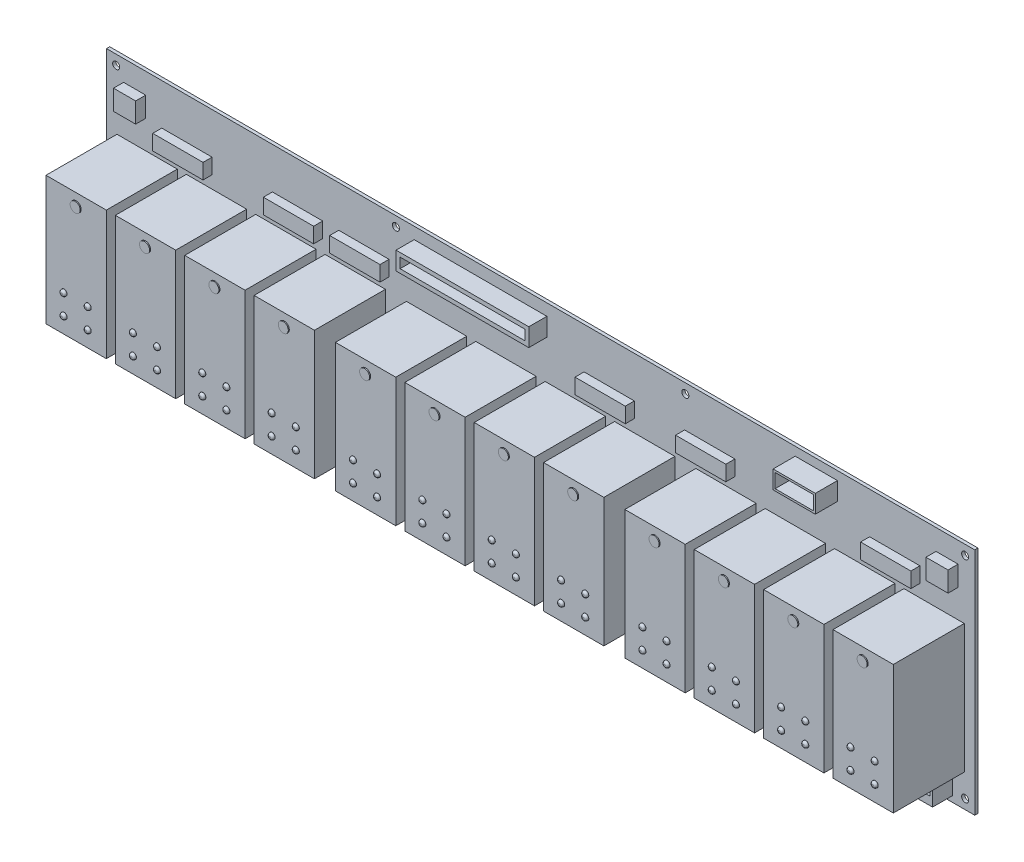
SolidWorks part; units mm, degrees
ref_plane "Front Plane" through (0, 0, 0) normal (0, 0, 1) x (1, 0, 0)
ref_plane "Top Plane" through (0, 0, 0) normal (0, 1, 0) x (1, 0, 0)
ref_plane "Right Plane" through (0, 0, 0) normal (1, 0, 0) x (0, 0, -1)
sketch "Sketch1" plane through (0, 0, 0) normal (0, 0, 1) x (1, 0, 0)
  line L1 (0, 0) -> (431.8, 0)
  line L2 (0, 0) -> (0, 114.3)
  line L3 (0, 114.3) -> (431.8, 114.3)
  line L4 (431.8, 0) -> (431.8, 114.3)
extrude "PCB" add sketch "Sketch1" along normal blind 1.6
ref_plane "Plane_z1_6" through (0, 0, 1.6) normal (0, 0, 1) x (1, 0, 0)
sketch "Sketch2" plane through (0, 0, 1.6) normal (0, 0, 1) x (1, 0, 0)
  line L1 (27.5, 86.2) -> (52.5, 86.2)
  line L2 (27.5, 86.2) -> (27.5, 93.8)
  line L3 (27.5, 93.8) -> (52.5, 93.8)
  line L4 (52.5, 86.2) -> (52.5, 93.8)
  line L6 (82.5, 86.2) -> (107.5, 86.2)
  line L7 (82.5, 86.2) -> (82.5, 93.8)
  line L8 (82.5, 93.8) -> (107.5, 93.8)
  line L9 (107.5, 86.2) -> (107.5, 93.8)
  line L11 (115.5, 86.2) -> (140.5, 86.2)
  line L12 (115.5, 86.2) -> (115.5, 93.8)
  line L13 (115.5, 93.8) -> (140.5, 93.8)
  line L14 (140.5, 86.2) -> (140.5, 93.8)
  line L16 (237.5, 86.2) -> (262.5, 86.2)
  line L17 (237.5, 86.2) -> (237.5, 93.8)
  line L18 (237.5, 93.8) -> (262.5, 93.8)
  line L19 (262.5, 86.2) -> (262.5, 93.8)
  line L21 (287.5, 86.2) -> (312.5, 86.2)
  line L22 (287.5, 86.2) -> (287.5, 93.8)
  line L23 (287.5, 93.8) -> (312.5, 93.8)
  line L24 (312.5, 86.2) -> (312.5, 93.8)
  line L26 (379.5, 86.2) -> (404.5, 86.2)
  line L27 (379.5, 86.2) -> (379.5, 93.8)
  line L28 (379.5, 93.8) -> (404.5, 93.8)
  line L29 (404.5, 86.2) -> (404.5, 93.8)
extrude "Body00" add sketch "Sketch2" along normal blind 4.5
sketch "Sketch3" plane through (0, 0, 1.6) normal (0, 0, 1) x (1, 0, 0)
  line L1 (8.5, 94) -> (19.5, 94)
  line L2 (8.5, 94) -> (8.5, 104)
  line L3 (8.5, 104) -> (19.5, 104)
  line L4 (19.5, 94) -> (19.5, 104)
  line L6 (412.5, 94) -> (423.5, 94)
  line L7 (412.5, 94) -> (412.5, 104)
  line L8 (412.5, 104) -> (423.5, 104)
  line L9 (423.5, 94) -> (423.5, 104)
extrude "Body01" add sketch "Sketch3" along normal blind 5
sketch "Sketch4" plane through (0, 0, 1.6) normal (0, 0, 1) x (1, 0, 0)
  line L1 (153, 99.5) -> (219, 99.5)
  line L2 (153, 99.5) -> (153, 108.5)
  line L3 (153, 108.5) -> (219, 108.5)
  line L4 (219, 99.5) -> (219, 108.5)
extrude "Body02" add sketch "Sketch4" along normal blind 9
sketch "Sketch5" plane through (0, 0, 1.6) normal (0, 0, 1) x (1, 0, 0)
  line L1 (11.007, 3) -> (132.927, 3)
  line L2 (11.007, 3) -> (11.007, 12)
  line L3 (11.007, 12) -> (132.927, 12)
  line L4 (132.927, 3) -> (132.927, 12)
  line L6 (154.94, 3) -> (276.86, 3)
  line L7 (154.94, 3) -> (154.94, 12)
  line L8 (154.94, 12) -> (276.86, 12)
  line L9 (276.86, 3) -> (276.86, 12)
  line L11 (298.873, 3) -> (420.793, 3)
  line L12 (298.873, 3) -> (298.873, 12)
  line L13 (298.873, 12) -> (420.793, 12)
  line L14 (420.793, 3) -> (420.793, 12)
extrude "Body03" add sketch "Sketch5" along normal blind 10
sketch "Sketch6" plane through (0, 0, 1.6) normal (0, 0, 1) x (1, 0, 0)
  line L1 (342.5, 101) -> (363.5, 101)
  line L2 (342.5, 101) -> (342.5, 110)
  line L3 (342.5, 110) -> (363.5, 110)
  line L4 (363.5, 101) -> (363.5, 110)
extrude "Body04" add sketch "Sketch6" along normal blind 11
sketch "Sketch7" plane through (0, 0, 1.6) normal (0, 0, 1) x (1, 0, 0)
  line L1 (5.217, 16) -> (35.217, 16)
  line L2 (5.217, 16) -> (5.217, 80)
  line L3 (5.217, 80) -> (35.217, 80)
  line L4 (35.217, 16) -> (35.217, 80)
  line L6 (39.717, 16) -> (69.717, 16)
  line L7 (39.717, 16) -> (39.717, 80)
  line L8 (39.717, 80) -> (69.717, 80)
  line L9 (69.717, 16) -> (69.717, 80)
  line L11 (74.217, 16) -> (104.217, 16)
  line L12 (74.217, 16) -> (74.217, 80)
  line L13 (74.217, 80) -> (104.217, 80)
  line L14 (104.217, 16) -> (104.217, 80)
  line L16 (108.717, 16) -> (138.717, 16)
  line L17 (108.717, 16) -> (108.717, 80)
  line L18 (108.717, 80) -> (138.717, 80)
  line L19 (138.717, 16) -> (138.717, 80)
  line L21 (149.15, 16) -> (179.15, 16)
  line L22 (149.15, 16) -> (149.15, 80)
  line L23 (149.15, 80) -> (179.15, 80)
  line L24 (179.15, 16) -> (179.15, 80)
  line L26 (183.65, 16) -> (213.65, 16)
  line L27 (183.65, 16) -> (183.65, 80)
  line L28 (183.65, 80) -> (213.65, 80)
  line L29 (213.65, 16) -> (213.65, 80)
  line L31 (218.15, 16) -> (248.15, 16)
  line L32 (218.15, 16) -> (218.15, 80)
  line L33 (218.15, 80) -> (248.15, 80)
  line L34 (248.15, 16) -> (248.15, 80)
  line L36 (252.65, 16) -> (282.65, 16)
  line L37 (252.65, 16) -> (252.65, 80)
  line L38 (252.65, 80) -> (282.65, 80)
  line L39 (282.65, 16) -> (282.65, 80)
  line L41 (293.083, 16) -> (323.083, 16)
  line L42 (293.083, 16) -> (293.083, 80)
  line L43 (293.083, 80) -> (323.083, 80)
  line L44 (323.083, 16) -> (323.083, 80)
  line L46 (327.583, 16) -> (357.583, 16)
  line L47 (327.583, 16) -> (327.583, 80)
  line L48 (327.583, 80) -> (357.583, 80)
  line L49 (357.583, 16) -> (357.583, 80)
  line L51 (362.083, 16) -> (392.083, 16)
  line L52 (362.083, 16) -> (362.083, 80)
  line L53 (362.083, 80) -> (392.083, 80)
  line L54 (392.083, 16) -> (392.083, 80)
  line L56 (396.583, 16) -> (426.583, 16)
  line L57 (396.583, 16) -> (396.583, 80)
  line L58 (396.583, 80) -> (426.583, 80)
  line L59 (426.583, 16) -> (426.583, 80)
extrude "Body05" add sketch "Sketch7" along normal blind 35.3
ref_plane "Plane_z36_9" through (0, 0, 36.9) normal (0, 0, 1) x (1, 0, 0)
sketch "Sketch8" plane through (0, 0, 36.9) normal (0, 0, 1) x (1, 0, 0)
  circle A0 centre (20.217, 74) radius 2.5
  circle A1 centre (54.717, 74) radius 2.5
  circle A2 centre (89.217, 74) radius 2.5
  circle A3 centre (123.717, 74) radius 2.5
  circle A4 centre (164.15, 74) radius 2.5
  circle A5 centre (198.65, 74) radius 2.5
  circle A6 centre (233.15, 74) radius 2.5
  circle A7 centre (267.65, 74) radius 2.5
  circle A8 centre (308.083, 74) radius 2.5
  circle A9 centre (342.583, 74) radius 2.5
  circle A10 centre (377.083, 74) radius 2.5
  circle A11 centre (411.583, 74) radius 2.5
extrude "Body06" add sketch "Sketch8" along normal blind 0.5
sketch "Sketch9" plane through (0, 0, 36.9) normal (0, 0, 1) x (1, 0, 0)
  circle A0 centre (14.217, 24) radius 1.5
  circle A1 centre (14.217, 34) radius 1.5
  circle A2 centre (26.217, 24) radius 1.5
  circle A3 centre (26.217, 34) radius 1.5
  circle A4 centre (48.717, 24) radius 1.5
  circle A5 centre (48.717, 34) radius 1.5
  circle A6 centre (60.717, 24) radius 1.5
  circle A7 centre (60.717, 34) radius 1.5
  circle A8 centre (83.217, 24) radius 1.5
  circle A9 centre (83.217, 34) radius 1.5
  circle A10 centre (95.217, 24) radius 1.5
  circle A11 centre (95.217, 34) radius 1.5
  circle A12 centre (117.717, 24) radius 1.5
  circle A13 centre (117.717, 34) radius 1.5
  circle A14 centre (129.717, 24) radius 1.5
  circle A15 centre (129.717, 34) radius 1.5
  circle A16 centre (158.15, 24) radius 1.5
  circle A17 centre (158.15, 34) radius 1.5
  circle A18 centre (170.15, 24) radius 1.5
  circle A19 centre (170.15, 34) radius 1.5
  circle A20 centre (192.65, 24) radius 1.5
  circle A21 centre (192.65, 34) radius 1.5
  circle A22 centre (204.65, 24) radius 1.5
  circle A23 centre (204.65, 34) radius 1.5
  circle A24 centre (227.15, 24) radius 1.5
  circle A25 centre (227.15, 34) radius 1.5
  circle A26 centre (239.15, 24) radius 1.5
  circle A27 centre (239.15, 34) radius 1.5
  circle A28 centre (261.65, 24) radius 1.5
  circle A29 centre (261.65, 34) radius 1.5
  circle A30 centre (273.65, 24) radius 1.5
  circle A31 centre (273.65, 34) radius 1.5
  circle A32 centre (302.083, 24) radius 1.5
  circle A33 centre (302.083, 34) radius 1.5
  circle A34 centre (314.083, 24) radius 1.5
  circle A35 centre (314.083, 34) radius 1.5
  circle A36 centre (336.583, 24) radius 1.5
  circle A37 centre (336.583, 34) radius 1.5
  circle A38 centre (348.583, 24) radius 1.5
  circle A39 centre (348.583, 34) radius 1.5
  circle A40 centre (371.083, 24) radius 1.5
  circle A41 centre (371.083, 34) radius 1.5
  circle A42 centre (383.083, 24) radius 1.5
  circle A43 centre (383.083, 34) radius 1.5
  circle A44 centre (405.583, 24) radius 1.5
  circle A45 centre (405.583, 34) radius 1.5
  circle A46 centre (417.583, 24) radius 1.5
  circle A47 centre (417.583, 34) radius 1.5
extrude "Body07" add sketch "Sketch9" along normal blind 1.2
ref_plane "Plane_y7" through (0, 7, 0) normal (0, 1, 0) x (1, 0, 0)
sketch "Sketch10" plane through (0, 7, 0) normal (0, 1, 0) x (1, 0, 0)
  line L1 (11.947, -3.5) -> (15.147, -3.5)
  line L2 (11.947, -3.5) -> (11.947, -6.7)
  line L3 (11.947, -6.7) -> (15.147, -6.7)
  line L4 (15.147, -3.5) -> (15.147, -6.7)
  line L6 (17.027, -3.5) -> (20.227, -3.5)
  line L7 (17.027, -3.5) -> (17.027, -6.7)
  line L8 (17.027, -6.7) -> (20.227, -6.7)
  line L9 (20.227, -3.5) -> (20.227, -6.7)
  line L11 (22.107, -3.5) -> (25.307, -3.5)
  line L12 (22.107, -3.5) -> (22.107, -6.7)
  line L13 (22.107, -6.7) -> (25.307, -6.7)
  line L14 (25.307, -3.5) -> (25.307, -6.7)
  line L16 (27.187, -3.5) -> (30.387, -3.5)
  line L17 (27.187, -3.5) -> (27.187, -6.7)
  line L18 (27.187, -6.7) -> (30.387, -6.7)
  line L19 (30.387, -3.5) -> (30.387, -6.7)
  line L21 (32.267, -3.5) -> (35.467, -3.5)
  line L22 (32.267, -3.5) -> (32.267, -6.7)
  line L23 (32.267, -6.7) -> (35.467, -6.7)
  line L24 (35.467, -3.5) -> (35.467, -6.7)
  line L26 (37.347, -3.5) -> (40.547, -3.5)
  line L27 (37.347, -3.5) -> (37.347, -6.7)
  line L28 (37.347, -6.7) -> (40.547, -6.7)
  line L29 (40.547, -3.5) -> (40.547, -6.7)
  line L31 (42.427, -3.5) -> (45.627, -3.5)
  line L32 (42.427, -3.5) -> (42.427, -6.7)
  line L33 (42.427, -6.7) -> (45.627, -6.7)
  line L34 (45.627, -3.5) -> (45.627, -6.7)
  line L36 (47.507, -3.5) -> (50.707, -3.5)
  line L37 (47.507, -3.5) -> (47.507, -6.7)
  line L38 (47.507, -6.7) -> (50.707, -6.7)
  line L39 (50.707, -3.5) -> (50.707, -6.7)
  line L41 (52.587, -3.5) -> (55.787, -3.5)
  line L42 (52.587, -3.5) -> (52.587, -6.7)
  line L43 (52.587, -6.7) -> (55.787, -6.7)
  line L44 (55.787, -3.5) -> (55.787, -6.7)
  line L46 (57.667, -3.5) -> (60.867, -3.5)
  line L47 (57.667, -3.5) -> (57.667, -6.7)
  line L48 (57.667, -6.7) -> (60.867, -6.7)
  line L49 (60.867, -3.5) -> (60.867, -6.7)
  line L51 (62.747, -3.5) -> (65.947, -3.5)
  line L52 (62.747, -3.5) -> (62.747, -6.7)
  line L53 (62.747, -6.7) -> (65.947, -6.7)
  line L54 (65.947, -3.5) -> (65.947, -6.7)
  line L56 (67.827, -3.5) -> (71.027, -3.5)
  line L57 (67.827, -3.5) -> (67.827, -6.7)
  line L58 (67.827, -6.7) -> (71.027, -6.7)
  line L59 (71.027, -3.5) -> (71.027, -6.7)
  line L61 (72.907, -3.5) -> (76.107, -3.5)
  line L62 (72.907, -3.5) -> (72.907, -6.7)
  line L63 (72.907, -6.7) -> (76.107, -6.7)
  line L64 (76.107, -3.5) -> (76.107, -6.7)
  line L66 (77.987, -3.5) -> (81.187, -3.5)
  line L67 (77.987, -3.5) -> (77.987, -6.7)
  line L68 (77.987, -6.7) -> (81.187, -6.7)
  line L69 (81.187, -3.5) -> (81.187, -6.7)
  line L71 (83.067, -3.5) -> (86.267, -3.5)
  line L72 (83.067, -3.5) -> (83.067, -6.7)
  line L73 (83.067, -6.7) -> (86.267, -6.7)
  line L74 (86.267, -3.5) -> (86.267, -6.7)
  line L76 (88.147, -3.5) -> (91.347, -3.5)
  line L77 (88.147, -3.5) -> (88.147, -6.7)
  line L78 (88.147, -6.7) -> (91.347, -6.7)
  line L79 (91.347, -3.5) -> (91.347, -6.7)
  line L81 (93.227, -3.5) -> (96.427, -3.5)
  line L82 (93.227, -3.5) -> (93.227, -6.7)
  line L83 (93.227, -6.7) -> (96.427, -6.7)
  line L84 (96.427, -3.5) -> (96.427, -6.7)
  line L86 (98.307, -3.5) -> (101.507, -3.5)
  line L87 (98.307, -3.5) -> (98.307, -6.7)
  line L88 (98.307, -6.7) -> (101.507, -6.7)
  line L89 (101.507, -3.5) -> (101.507, -6.7)
  line L91 (103.387, -3.5) -> (106.587, -3.5)
  line L92 (103.387, -3.5) -> (103.387, -6.7)
  line L93 (103.387, -6.7) -> (106.587, -6.7)
  line L94 (106.587, -3.5) -> (106.587, -6.7)
  line L96 (108.467, -3.5) -> (111.667, -3.5)
  line L97 (108.467, -3.5) -> (108.467, -6.7)
  line L98 (108.467, -6.7) -> (111.667, -6.7)
  line L99 (111.667, -3.5) -> (111.667, -6.7)
  line L101 (113.547, -3.5) -> (116.747, -3.5)
  line L102 (113.547, -3.5) -> (113.547, -6.7)
  line L103 (113.547, -6.7) -> (116.747, -6.7)
  line L104 (116.747, -3.5) -> (116.747, -6.7)
  line L106 (118.627, -3.5) -> (121.827, -3.5)
  line L107 (118.627, -3.5) -> (118.627, -6.7)
  line L108 (118.627, -6.7) -> (121.827, -6.7)
  line L109 (121.827, -3.5) -> (121.827, -6.7)
  line L111 (123.707, -3.5) -> (126.907, -3.5)
  line L112 (123.707, -3.5) -> (123.707, -6.7)
  line L113 (123.707, -6.7) -> (126.907, -6.7)
  line L114 (126.907, -3.5) -> (126.907, -6.7)
  line L116 (128.787, -3.5) -> (131.987, -3.5)
  line L117 (128.787, -3.5) -> (128.787, -6.7)
  line L118 (128.787, -6.7) -> (131.987, -6.7)
  line L119 (131.987, -3.5) -> (131.987, -6.7)
  line L121 (155.88, -3.5) -> (159.08, -3.5)
  line L122 (155.88, -3.5) -> (155.88, -6.7)
  line L123 (155.88, -6.7) -> (159.08, -6.7)
  line L124 (159.08, -3.5) -> (159.08, -6.7)
  line L126 (160.96, -3.5) -> (164.16, -3.5)
  line L127 (160.96, -3.5) -> (160.96, -6.7)
  line L128 (160.96, -6.7) -> (164.16, -6.7)
  line L129 (164.16, -3.5) -> (164.16, -6.7)
  line L131 (166.04, -3.5) -> (169.24, -3.5)
  line L132 (166.04, -3.5) -> (166.04, -6.7)
  line L133 (166.04, -6.7) -> (169.24, -6.7)
  line L134 (169.24, -3.5) -> (169.24, -6.7)
  line L136 (171.12, -3.5) -> (174.32, -3.5)
  line L137 (171.12, -3.5) -> (171.12, -6.7)
  line L138 (171.12, -6.7) -> (174.32, -6.7)
  line L139 (174.32, -3.5) -> (174.32, -6.7)
  line L141 (176.2, -3.5) -> (179.4, -3.5)
  line L142 (176.2, -3.5) -> (176.2, -6.7)
  line L143 (176.2, -6.7) -> (179.4, -6.7)
  line L144 (179.4, -3.5) -> (179.4, -6.7)
  line L146 (181.28, -3.5) -> (184.48, -3.5)
  line L147 (181.28, -3.5) -> (181.28, -6.7)
  line L148 (181.28, -6.7) -> (184.48, -6.7)
  line L149 (184.48, -3.5) -> (184.48, -6.7)
  line L151 (186.36, -3.5) -> (189.56, -3.5)
  line L152 (186.36, -3.5) -> (186.36, -6.7)
  line L153 (186.36, -6.7) -> (189.56, -6.7)
  line L154 (189.56, -3.5) -> (189.56, -6.7)
  line L156 (191.44, -3.5) -> (194.64, -3.5)
  line L157 (191.44, -3.5) -> (191.44, -6.7)
  line L158 (191.44, -6.7) -> (194.64, -6.7)
  line L159 (194.64, -3.5) -> (194.64, -6.7)
  line L161 (196.52, -3.5) -> (199.72, -3.5)
  line L162 (196.52, -3.5) -> (196.52, -6.7)
  line L163 (196.52, -6.7) -> (199.72, -6.7)
  line L164 (199.72, -3.5) -> (199.72, -6.7)
  line L166 (201.6, -3.5) -> (204.8, -3.5)
  line L167 (201.6, -3.5) -> (201.6, -6.7)
  line L168 (201.6, -6.7) -> (204.8, -6.7)
  line L169 (204.8, -3.5) -> (204.8, -6.7)
  line L171 (206.68, -3.5) -> (209.88, -3.5)
  line L172 (206.68, -3.5) -> (206.68, -6.7)
  line L173 (206.68, -6.7) -> (209.88, -6.7)
  line L174 (209.88, -3.5) -> (209.88, -6.7)
  line L176 (211.76, -3.5) -> (214.96, -3.5)
  line L177 (211.76, -3.5) -> (211.76, -6.7)
  line L178 (211.76, -6.7) -> (214.96, -6.7)
  line L179 (214.96, -3.5) -> (214.96, -6.7)
  line L181 (216.84, -3.5) -> (220.04, -3.5)
  line L182 (216.84, -3.5) -> (216.84, -6.7)
  line L183 (216.84, -6.7) -> (220.04, -6.7)
  line L184 (220.04, -3.5) -> (220.04, -6.7)
  line L186 (221.92, -3.5) -> (225.12, -3.5)
  line L187 (221.92, -3.5) -> (221.92, -6.7)
  line L188 (221.92, -6.7) -> (225.12, -6.7)
  line L189 (225.12, -3.5) -> (225.12, -6.7)
  line L191 (227, -3.5) -> (230.2, -3.5)
  line L192 (227, -3.5) -> (227, -6.7)
  line L193 (227, -6.7) -> (230.2, -6.7)
  line L194 (230.2, -3.5) -> (230.2, -6.7)
  line L196 (232.08, -3.5) -> (235.28, -3.5)
  line L197 (232.08, -3.5) -> (232.08, -6.7)
  line L198 (232.08, -6.7) -> (235.28, -6.7)
  line L199 (235.28, -3.5) -> (235.28, -6.7)
  line L201 (237.16, -3.5) -> (240.36, -3.5)
  line L202 (237.16, -3.5) -> (237.16, -6.7)
  line L203 (237.16, -6.7) -> (240.36, -6.7)
  line L204 (240.36, -3.5) -> (240.36, -6.7)
  line L206 (242.24, -3.5) -> (245.44, -3.5)
  line L207 (242.24, -3.5) -> (242.24, -6.7)
  line L208 (242.24, -6.7) -> (245.44, -6.7)
  line L209 (245.44, -3.5) -> (245.44, -6.7)
  line L211 (247.32, -3.5) -> (250.52, -3.5)
  line L212 (247.32, -3.5) -> (247.32, -6.7)
  line L213 (247.32, -6.7) -> (250.52, -6.7)
  line L214 (250.52, -3.5) -> (250.52, -6.7)
  line L216 (252.4, -3.5) -> (255.6, -3.5)
  line L217 (252.4, -3.5) -> (252.4, -6.7)
  line L218 (252.4, -6.7) -> (255.6, -6.7)
  line L219 (255.6, -3.5) -> (255.6, -6.7)
  line L221 (257.48, -3.5) -> (260.68, -3.5)
  line L222 (257.48, -3.5) -> (257.48, -6.7)
  line L223 (257.48, -6.7) -> (260.68, -6.7)
  line L224 (260.68, -3.5) -> (260.68, -6.7)
  line L226 (262.56, -3.5) -> (265.76, -3.5)
  line L227 (262.56, -3.5) -> (262.56, -6.7)
  line L228 (262.56, -6.7) -> (265.76, -6.7)
  line L229 (265.76, -3.5) -> (265.76, -6.7)
  line L231 (267.64, -3.5) -> (270.84, -3.5)
  line L232 (267.64, -3.5) -> (267.64, -6.7)
  line L233 (267.64, -6.7) -> (270.84, -6.7)
  line L234 (270.84, -3.5) -> (270.84, -6.7)
  line L236 (272.72, -3.5) -> (275.92, -3.5)
  line L237 (272.72, -3.5) -> (272.72, -6.7)
  line L238 (272.72, -6.7) -> (275.92, -6.7)
  line L239 (275.92, -3.5) -> (275.92, -6.7)
  line L241 (299.813, -3.5) -> (303.013, -3.5)
  line L242 (299.813, -3.5) -> (299.813, -6.7)
  line L243 (299.813, -6.7) -> (303.013, -6.7)
  line L244 (303.013, -3.5) -> (303.013, -6.7)
  line L246 (304.893, -3.5) -> (308.093, -3.5)
  line L247 (304.893, -3.5) -> (304.893, -6.7)
  line L248 (304.893, -6.7) -> (308.093, -6.7)
  line L249 (308.093, -3.5) -> (308.093, -6.7)
  line L251 (309.973, -3.5) -> (313.173, -3.5)
  line L252 (309.973, -3.5) -> (309.973, -6.7)
  line L253 (309.973, -6.7) -> (313.173, -6.7)
  line L254 (313.173, -3.5) -> (313.173, -6.7)
  line L256 (315.053, -3.5) -> (318.253, -3.5)
  line L257 (315.053, -3.5) -> (315.053, -6.7)
  line L258 (315.053, -6.7) -> (318.253, -6.7)
  line L259 (318.253, -3.5) -> (318.253, -6.7)
  line L261 (320.133, -3.5) -> (323.333, -3.5)
  line L262 (320.133, -3.5) -> (320.133, -6.7)
  line L263 (320.133, -6.7) -> (323.333, -6.7)
  line L264 (323.333, -3.5) -> (323.333, -6.7)
  line L266 (325.213, -3.5) -> (328.413, -3.5)
  line L267 (325.213, -3.5) -> (325.213, -6.7)
  line L268 (325.213, -6.7) -> (328.413, -6.7)
  line L269 (328.413, -3.5) -> (328.413, -6.7)
  line L271 (330.293, -3.5) -> (333.493, -3.5)
  line L272 (330.293, -3.5) -> (330.293, -6.7)
  line L273 (330.293, -6.7) -> (333.493, -6.7)
  line L274 (333.493, -3.5) -> (333.493, -6.7)
  line L276 (335.373, -3.5) -> (338.573, -3.5)
  line L277 (335.373, -3.5) -> (335.373, -6.7)
  line L278 (335.373, -6.7) -> (338.573, -6.7)
  line L279 (338.573, -3.5) -> (338.573, -6.7)
  line L281 (340.453, -3.5) -> (343.653, -3.5)
  line L282 (340.453, -3.5) -> (340.453, -6.7)
  line L283 (340.453, -6.7) -> (343.653, -6.7)
  line L284 (343.653, -3.5) -> (343.653, -6.7)
  line L286 (345.533, -3.5) -> (348.733, -3.5)
  line L287 (345.533, -3.5) -> (345.533, -6.7)
  line L288 (345.533, -6.7) -> (348.733, -6.7)
  line L289 (348.733, -3.5) -> (348.733, -6.7)
  line L291 (350.613, -3.5) -> (353.813, -3.5)
  line L292 (350.613, -3.5) -> (350.613, -6.7)
  line L293 (350.613, -6.7) -> (353.813, -6.7)
  line L294 (353.813, -3.5) -> (353.813, -6.7)
  line L296 (355.693, -3.5) -> (358.893, -3.5)
  line L297 (355.693, -3.5) -> (355.693, -6.7)
  line L298 (355.693, -6.7) -> (358.893, -6.7)
  line L299 (358.893, -3.5) -> (358.893, -6.7)
  line L301 (360.773, -3.5) -> (363.973, -3.5)
  line L302 (360.773, -3.5) -> (360.773, -6.7)
  line L303 (360.773, -6.7) -> (363.973, -6.7)
  line L304 (363.973, -3.5) -> (363.973, -6.7)
  line L306 (365.853, -3.5) -> (369.053, -3.5)
  line L307 (365.853, -3.5) -> (365.853, -6.7)
  line L308 (365.853, -6.7) -> (369.053, -6.7)
  line L309 (369.053, -3.5) -> (369.053, -6.7)
  line L311 (370.933, -3.5) -> (374.133, -3.5)
  line L312 (370.933, -3.5) -> (370.933, -6.7)
  line L313 (370.933, -6.7) -> (374.133, -6.7)
  line L314 (374.133, -3.5) -> (374.133, -6.7)
  line L316 (376.013, -3.5) -> (379.213, -3.5)
  line L317 (376.013, -3.5) -> (376.013, -6.7)
  line L318 (376.013, -6.7) -> (379.213, -6.7)
  line L319 (379.213, -3.5) -> (379.213, -6.7)
  line L321 (381.093, -3.5) -> (384.293, -3.5)
  line L322 (381.093, -3.5) -> (381.093, -6.7)
  line L323 (381.093, -6.7) -> (384.293, -6.7)
  line L324 (384.293, -3.5) -> (384.293, -6.7)
  line L326 (386.173, -3.5) -> (389.373, -3.5)
  line L327 (386.173, -3.5) -> (386.173, -6.7)
  line L328 (386.173, -6.7) -> (389.373, -6.7)
  line L329 (389.373, -3.5) -> (389.373, -6.7)
  line L331 (391.253, -3.5) -> (394.453, -3.5)
  line L332 (391.253, -3.5) -> (391.253, -6.7)
  line L333 (391.253, -6.7) -> (394.453, -6.7)
  line L334 (394.453, -3.5) -> (394.453, -6.7)
  line L336 (396.333, -3.5) -> (399.533, -3.5)
  line L337 (396.333, -3.5) -> (396.333, -6.7)
  line L338 (396.333, -6.7) -> (399.533, -6.7)
  line L339 (399.533, -3.5) -> (399.533, -6.7)
  line L341 (401.413, -3.5) -> (404.613, -3.5)
  line L342 (401.413, -3.5) -> (401.413, -6.7)
  line L343 (401.413, -6.7) -> (404.613, -6.7)
  line L344 (404.613, -3.5) -> (404.613, -6.7)
  line L346 (406.493, -3.5) -> (409.693, -3.5)
  line L347 (406.493, -3.5) -> (406.493, -6.7)
  line L348 (406.493, -6.7) -> (409.693, -6.7)
  line L349 (409.693, -3.5) -> (409.693, -6.7)
  line L351 (411.573, -3.5) -> (414.773, -3.5)
  line L352 (411.573, -3.5) -> (411.573, -6.7)
  line L353 (411.573, -6.7) -> (414.773, -6.7)
  line L354 (414.773, -3.5) -> (414.773, -6.7)
  line L356 (416.653, -3.5) -> (419.853, -3.5)
  line L357 (416.653, -3.5) -> (416.653, -6.7)
  line L358 (416.653, -6.7) -> (419.853, -6.7)
  line L359 (419.853, -3.5) -> (419.853, -6.7)
extrude "Cut00" cut sketch "Sketch10" against normal blind 4
ref_plane "Plane_z10_6" through (0, 0, 10.6) normal (0, 0, 1) x (1, 0, 0)
sketch "Sketch11" plane through (0, 0, 10.6) normal (0, 0, 1) x (1, 0, 0)
  line L1 (155, 101.5) -> (217, 101.5)
  line L2 (155, 101.5) -> (155, 106.5)
  line L3 (155, 106.5) -> (217, 106.5)
  line L4 (217, 101.5) -> (217, 106.5)
extrude "Cut01" cut sketch "Sketch11" against normal blind 7
ref_plane "Plane_z11_6" through (0, 0, 11.6) normal (0, 0, 1) x (1, 0, 0)
sketch "Sketch12" plane through (0, 0, 11.6) normal (0, 0, 1) x (1, 0, 0)
  line L1 (12.147, 7.1) -> (14.947, 7.1)
  line L2 (12.147, 7.1) -> (12.147, 9.9)
  line L3 (12.147, 9.9) -> (14.947, 9.9)
  line L4 (14.947, 7.1) -> (14.947, 9.9)
  line L6 (17.227, 7.1) -> (20.027, 7.1)
  line L7 (17.227, 7.1) -> (17.227, 9.9)
  line L8 (17.227, 9.9) -> (20.027, 9.9)
  line L9 (20.027, 7.1) -> (20.027, 9.9)
  line L11 (22.307, 7.1) -> (25.107, 7.1)
  line L12 (22.307, 7.1) -> (22.307, 9.9)
  line L13 (22.307, 9.9) -> (25.107, 9.9)
  line L14 (25.107, 7.1) -> (25.107, 9.9)
  line L16 (27.387, 7.1) -> (30.187, 7.1)
  line L17 (27.387, 7.1) -> (27.387, 9.9)
  line L18 (27.387, 9.9) -> (30.187, 9.9)
  line L19 (30.187, 7.1) -> (30.187, 9.9)
  line L21 (32.467, 7.1) -> (35.267, 7.1)
  line L22 (32.467, 7.1) -> (32.467, 9.9)
  line L23 (32.467, 9.9) -> (35.267, 9.9)
  line L24 (35.267, 7.1) -> (35.267, 9.9)
  line L26 (37.547, 7.1) -> (40.347, 7.1)
  line L27 (37.547, 7.1) -> (37.547, 9.9)
  line L28 (37.547, 9.9) -> (40.347, 9.9)
  line L29 (40.347, 7.1) -> (40.347, 9.9)
  line L31 (42.627, 7.1) -> (45.427, 7.1)
  line L32 (42.627, 7.1) -> (42.627, 9.9)
  line L33 (42.627, 9.9) -> (45.427, 9.9)
  line L34 (45.427, 7.1) -> (45.427, 9.9)
  line L36 (47.707, 7.1) -> (50.507, 7.1)
  line L37 (47.707, 7.1) -> (47.707, 9.9)
  line L38 (47.707, 9.9) -> (50.507, 9.9)
  line L39 (50.507, 7.1) -> (50.507, 9.9)
  line L41 (52.787, 7.1) -> (55.587, 7.1)
  line L42 (52.787, 7.1) -> (52.787, 9.9)
  line L43 (52.787, 9.9) -> (55.587, 9.9)
  line L44 (55.587, 7.1) -> (55.587, 9.9)
  line L46 (57.867, 7.1) -> (60.667, 7.1)
  line L47 (57.867, 7.1) -> (57.867, 9.9)
  line L48 (57.867, 9.9) -> (60.667, 9.9)
  line L49 (60.667, 7.1) -> (60.667, 9.9)
  line L51 (62.947, 7.1) -> (65.747, 7.1)
  line L52 (62.947, 7.1) -> (62.947, 9.9)
  line L53 (62.947, 9.9) -> (65.747, 9.9)
  line L54 (65.747, 7.1) -> (65.747, 9.9)
  line L56 (68.027, 7.1) -> (70.827, 7.1)
  line L57 (68.027, 7.1) -> (68.027, 9.9)
  line L58 (68.027, 9.9) -> (70.827, 9.9)
  line L59 (70.827, 7.1) -> (70.827, 9.9)
  line L61 (73.107, 7.1) -> (75.907, 7.1)
  line L62 (73.107, 7.1) -> (73.107, 9.9)
  line L63 (73.107, 9.9) -> (75.907, 9.9)
  line L64 (75.907, 7.1) -> (75.907, 9.9)
  line L66 (78.187, 7.1) -> (80.987, 7.1)
  line L67 (78.187, 7.1) -> (78.187, 9.9)
  line L68 (78.187, 9.9) -> (80.987, 9.9)
  line L69 (80.987, 7.1) -> (80.987, 9.9)
  line L71 (83.267, 7.1) -> (86.067, 7.1)
  line L72 (83.267, 7.1) -> (83.267, 9.9)
  line L73 (83.267, 9.9) -> (86.067, 9.9)
  line L74 (86.067, 7.1) -> (86.067, 9.9)
  line L76 (88.347, 7.1) -> (91.147, 7.1)
  line L77 (88.347, 7.1) -> (88.347, 9.9)
  line L78 (88.347, 9.9) -> (91.147, 9.9)
  line L79 (91.147, 7.1) -> (91.147, 9.9)
  line L81 (93.427, 7.1) -> (96.227, 7.1)
  line L82 (93.427, 7.1) -> (93.427, 9.9)
  line L83 (93.427, 9.9) -> (96.227, 9.9)
  line L84 (96.227, 7.1) -> (96.227, 9.9)
  line L86 (98.507, 7.1) -> (101.307, 7.1)
  line L87 (98.507, 7.1) -> (98.507, 9.9)
  line L88 (98.507, 9.9) -> (101.307, 9.9)
  line L89 (101.307, 7.1) -> (101.307, 9.9)
  line L91 (103.587, 7.1) -> (106.387, 7.1)
  line L92 (103.587, 7.1) -> (103.587, 9.9)
  line L93 (103.587, 9.9) -> (106.387, 9.9)
  line L94 (106.387, 7.1) -> (106.387, 9.9)
  line L96 (108.667, 7.1) -> (111.467, 7.1)
  line L97 (108.667, 7.1) -> (108.667, 9.9)
  line L98 (108.667, 9.9) -> (111.467, 9.9)
  line L99 (111.467, 7.1) -> (111.467, 9.9)
  line L101 (113.747, 7.1) -> (116.547, 7.1)
  line L102 (113.747, 7.1) -> (113.747, 9.9)
  line L103 (113.747, 9.9) -> (116.547, 9.9)
  line L104 (116.547, 7.1) -> (116.547, 9.9)
  line L106 (118.827, 7.1) -> (121.627, 7.1)
  line L107 (118.827, 7.1) -> (118.827, 9.9)
  line L108 (118.827, 9.9) -> (121.627, 9.9)
  line L109 (121.627, 7.1) -> (121.627, 9.9)
  line L111 (123.907, 7.1) -> (126.707, 7.1)
  line L112 (123.907, 7.1) -> (123.907, 9.9)
  line L113 (123.907, 9.9) -> (126.707, 9.9)
  line L114 (126.707, 7.1) -> (126.707, 9.9)
  line L116 (128.987, 7.1) -> (131.787, 7.1)
  line L117 (128.987, 7.1) -> (128.987, 9.9)
  line L118 (128.987, 9.9) -> (131.787, 9.9)
  line L119 (131.787, 7.1) -> (131.787, 9.9)
  line L121 (156.08, 7.1) -> (158.88, 7.1)
  line L122 (156.08, 7.1) -> (156.08, 9.9)
  line L123 (156.08, 9.9) -> (158.88, 9.9)
  line L124 (158.88, 7.1) -> (158.88, 9.9)
  line L126 (161.16, 7.1) -> (163.96, 7.1)
  line L127 (161.16, 7.1) -> (161.16, 9.9)
  line L128 (161.16, 9.9) -> (163.96, 9.9)
  line L129 (163.96, 7.1) -> (163.96, 9.9)
  line L131 (166.24, 7.1) -> (169.04, 7.1)
  line L132 (166.24, 7.1) -> (166.24, 9.9)
  line L133 (166.24, 9.9) -> (169.04, 9.9)
  line L134 (169.04, 7.1) -> (169.04, 9.9)
  line L136 (171.32, 7.1) -> (174.12, 7.1)
  line L137 (171.32, 7.1) -> (171.32, 9.9)
  line L138 (171.32, 9.9) -> (174.12, 9.9)
  line L139 (174.12, 7.1) -> (174.12, 9.9)
  line L141 (176.4, 7.1) -> (179.2, 7.1)
  line L142 (176.4, 7.1) -> (176.4, 9.9)
  line L143 (176.4, 9.9) -> (179.2, 9.9)
  line L144 (179.2, 7.1) -> (179.2, 9.9)
  line L146 (181.48, 7.1) -> (184.28, 7.1)
  line L147 (181.48, 7.1) -> (181.48, 9.9)
  line L148 (181.48, 9.9) -> (184.28, 9.9)
  line L149 (184.28, 7.1) -> (184.28, 9.9)
  line L151 (186.56, 7.1) -> (189.36, 7.1)
  line L152 (186.56, 7.1) -> (186.56, 9.9)
  line L153 (186.56, 9.9) -> (189.36, 9.9)
  line L154 (189.36, 7.1) -> (189.36, 9.9)
  line L156 (191.64, 7.1) -> (194.44, 7.1)
  line L157 (191.64, 7.1) -> (191.64, 9.9)
  line L158 (191.64, 9.9) -> (194.44, 9.9)
  line L159 (194.44, 7.1) -> (194.44, 9.9)
  line L161 (196.72, 7.1) -> (199.52, 7.1)
  line L162 (196.72, 7.1) -> (196.72, 9.9)
  line L163 (196.72, 9.9) -> (199.52, 9.9)
  line L164 (199.52, 7.1) -> (199.52, 9.9)
  line L166 (201.8, 7.1) -> (204.6, 7.1)
  line L167 (201.8, 7.1) -> (201.8, 9.9)
  line L168 (201.8, 9.9) -> (204.6, 9.9)
  line L169 (204.6, 7.1) -> (204.6, 9.9)
  line L171 (206.88, 7.1) -> (209.68, 7.1)
  line L172 (206.88, 7.1) -> (206.88, 9.9)
  line L173 (206.88, 9.9) -> (209.68, 9.9)
  line L174 (209.68, 7.1) -> (209.68, 9.9)
  line L176 (211.96, 7.1) -> (214.76, 7.1)
  line L177 (211.96, 7.1) -> (211.96, 9.9)
  line L178 (211.96, 9.9) -> (214.76, 9.9)
  line L179 (214.76, 7.1) -> (214.76, 9.9)
  line L181 (217.04, 7.1) -> (219.84, 7.1)
  line L182 (217.04, 7.1) -> (217.04, 9.9)
  line L183 (217.04, 9.9) -> (219.84, 9.9)
  line L184 (219.84, 7.1) -> (219.84, 9.9)
  line L186 (222.12, 7.1) -> (224.92, 7.1)
  line L187 (222.12, 7.1) -> (222.12, 9.9)
  line L188 (222.12, 9.9) -> (224.92, 9.9)
  line L189 (224.92, 7.1) -> (224.92, 9.9)
  line L191 (227.2, 7.1) -> (230, 7.1)
  line L192 (227.2, 7.1) -> (227.2, 9.9)
  line L193 (227.2, 9.9) -> (230, 9.9)
  line L194 (230, 7.1) -> (230, 9.9)
  line L196 (232.28, 7.1) -> (235.08, 7.1)
  line L197 (232.28, 7.1) -> (232.28, 9.9)
  line L198 (232.28, 9.9) -> (235.08, 9.9)
  line L199 (235.08, 7.1) -> (235.08, 9.9)
  line L201 (237.36, 7.1) -> (240.16, 7.1)
  line L202 (237.36, 7.1) -> (237.36, 9.9)
  line L203 (237.36, 9.9) -> (240.16, 9.9)
  line L204 (240.16, 7.1) -> (240.16, 9.9)
  line L206 (242.44, 7.1) -> (245.24, 7.1)
  line L207 (242.44, 7.1) -> (242.44, 9.9)
  line L208 (242.44, 9.9) -> (245.24, 9.9)
  line L209 (245.24, 7.1) -> (245.24, 9.9)
  line L211 (247.52, 7.1) -> (250.32, 7.1)
  line L212 (247.52, 7.1) -> (247.52, 9.9)
  line L213 (247.52, 9.9) -> (250.32, 9.9)
  line L214 (250.32, 7.1) -> (250.32, 9.9)
  line L216 (252.6, 7.1) -> (255.4, 7.1)
  line L217 (252.6, 7.1) -> (252.6, 9.9)
  line L218 (252.6, 9.9) -> (255.4, 9.9)
  line L219 (255.4, 7.1) -> (255.4, 9.9)
  line L221 (257.68, 7.1) -> (260.48, 7.1)
  line L222 (257.68, 7.1) -> (257.68, 9.9)
  line L223 (257.68, 9.9) -> (260.48, 9.9)
  line L224 (260.48, 7.1) -> (260.48, 9.9)
  line L226 (262.76, 7.1) -> (265.56, 7.1)
  line L227 (262.76, 7.1) -> (262.76, 9.9)
  line L228 (262.76, 9.9) -> (265.56, 9.9)
  line L229 (265.56, 7.1) -> (265.56, 9.9)
  line L231 (267.84, 7.1) -> (270.64, 7.1)
  line L232 (267.84, 7.1) -> (267.84, 9.9)
  line L233 (267.84, 9.9) -> (270.64, 9.9)
  line L234 (270.64, 7.1) -> (270.64, 9.9)
  line L236 (272.92, 7.1) -> (275.72, 7.1)
  line L237 (272.92, 7.1) -> (272.92, 9.9)
  line L238 (272.92, 9.9) -> (275.72, 9.9)
  line L239 (275.72, 7.1) -> (275.72, 9.9)
  line L241 (300.013, 7.1) -> (302.813, 7.1)
  line L242 (300.013, 7.1) -> (300.013, 9.9)
  line L243 (300.013, 9.9) -> (302.813, 9.9)
  line L244 (302.813, 7.1) -> (302.813, 9.9)
  line L246 (305.093, 7.1) -> (307.893, 7.1)
  line L247 (305.093, 7.1) -> (305.093, 9.9)
  line L248 (305.093, 9.9) -> (307.893, 9.9)
  line L249 (307.893, 7.1) -> (307.893, 9.9)
  line L251 (310.173, 7.1) -> (312.973, 7.1)
  line L252 (310.173, 7.1) -> (310.173, 9.9)
  line L253 (310.173, 9.9) -> (312.973, 9.9)
  line L254 (312.973, 7.1) -> (312.973, 9.9)
  line L256 (315.253, 7.1) -> (318.053, 7.1)
  line L257 (315.253, 7.1) -> (315.253, 9.9)
  line L258 (315.253, 9.9) -> (318.053, 9.9)
  line L259 (318.053, 7.1) -> (318.053, 9.9)
  line L261 (320.333, 7.1) -> (323.133, 7.1)
  line L262 (320.333, 7.1) -> (320.333, 9.9)
  line L263 (320.333, 9.9) -> (323.133, 9.9)
  line L264 (323.133, 7.1) -> (323.133, 9.9)
  line L266 (325.413, 7.1) -> (328.213, 7.1)
  line L267 (325.413, 7.1) -> (325.413, 9.9)
  line L268 (325.413, 9.9) -> (328.213, 9.9)
  line L269 (328.213, 7.1) -> (328.213, 9.9)
  line L271 (330.493, 7.1) -> (333.293, 7.1)
  line L272 (330.493, 7.1) -> (330.493, 9.9)
  line L273 (330.493, 9.9) -> (333.293, 9.9)
  line L274 (333.293, 7.1) -> (333.293, 9.9)
  line L276 (335.573, 7.1) -> (338.373, 7.1)
  line L277 (335.573, 7.1) -> (335.573, 9.9)
  line L278 (335.573, 9.9) -> (338.373, 9.9)
  line L279 (338.373, 7.1) -> (338.373, 9.9)
  line L281 (340.653, 7.1) -> (343.453, 7.1)
  line L282 (340.653, 7.1) -> (340.653, 9.9)
  line L283 (340.653, 9.9) -> (343.453, 9.9)
  line L284 (343.453, 7.1) -> (343.453, 9.9)
  line L286 (345.733, 7.1) -> (348.533, 7.1)
  line L287 (345.733, 7.1) -> (345.733, 9.9)
  line L288 (345.733, 9.9) -> (348.533, 9.9)
  line L289 (348.533, 7.1) -> (348.533, 9.9)
  line L291 (350.813, 7.1) -> (353.613, 7.1)
  line L292 (350.813, 7.1) -> (350.813, 9.9)
  line L293 (350.813, 9.9) -> (353.613, 9.9)
  line L294 (353.613, 7.1) -> (353.613, 9.9)
  line L296 (355.893, 7.1) -> (358.693, 7.1)
  line L297 (355.893, 7.1) -> (355.893, 9.9)
  line L298 (355.893, 9.9) -> (358.693, 9.9)
  line L299 (358.693, 7.1) -> (358.693, 9.9)
  line L301 (360.973, 7.1) -> (363.773, 7.1)
  line L302 (360.973, 7.1) -> (360.973, 9.9)
  line L303 (360.973, 9.9) -> (363.773, 9.9)
  line L304 (363.773, 7.1) -> (363.773, 9.9)
  line L306 (366.053, 7.1) -> (368.853, 7.1)
  line L307 (366.053, 7.1) -> (366.053, 9.9)
  line L308 (366.053, 9.9) -> (368.853, 9.9)
  line L309 (368.853, 7.1) -> (368.853, 9.9)
  line L311 (371.133, 7.1) -> (373.933, 7.1)
  line L312 (371.133, 7.1) -> (371.133, 9.9)
  line L313 (371.133, 9.9) -> (373.933, 9.9)
  line L314 (373.933, 7.1) -> (373.933, 9.9)
  line L316 (376.213, 7.1) -> (379.013, 7.1)
  line L317 (376.213, 7.1) -> (376.213, 9.9)
  line L318 (376.213, 9.9) -> (379.013, 9.9)
  line L319 (379.013, 7.1) -> (379.013, 9.9)
  line L321 (381.293, 7.1) -> (384.093, 7.1)
  line L322 (381.293, 7.1) -> (381.293, 9.9)
  line L323 (381.293, 9.9) -> (384.093, 9.9)
  line L324 (384.093, 7.1) -> (384.093, 9.9)
  line L326 (386.373, 7.1) -> (389.173, 7.1)
  line L327 (386.373, 7.1) -> (386.373, 9.9)
  line L328 (386.373, 9.9) -> (389.173, 9.9)
  line L329 (389.173, 7.1) -> (389.173, 9.9)
  line L331 (391.453, 7.1) -> (394.253, 7.1)
  line L332 (391.453, 7.1) -> (391.453, 9.9)
  line L333 (391.453, 9.9) -> (394.253, 9.9)
  line L334 (394.253, 7.1) -> (394.253, 9.9)
  line L336 (396.533, 7.1) -> (399.333, 7.1)
  line L337 (396.533, 7.1) -> (396.533, 9.9)
  line L338 (396.533, 9.9) -> (399.333, 9.9)
  line L339 (399.333, 7.1) -> (399.333, 9.9)
  line L341 (401.613, 7.1) -> (404.413, 7.1)
  line L342 (401.613, 7.1) -> (401.613, 9.9)
  line L343 (401.613, 9.9) -> (404.413, 9.9)
  line L344 (404.413, 7.1) -> (404.413, 9.9)
  line L346 (406.693, 7.1) -> (409.493, 7.1)
  line L347 (406.693, 7.1) -> (406.693, 9.9)
  line L348 (406.693, 9.9) -> (409.493, 9.9)
  line L349 (409.493, 7.1) -> (409.493, 9.9)
  line L351 (411.773, 7.1) -> (414.573, 7.1)
  line L352 (411.773, 7.1) -> (411.773, 9.9)
  line L353 (411.773, 9.9) -> (414.573, 9.9)
  line L354 (414.573, 7.1) -> (414.573, 9.9)
  line L356 (416.853, 7.1) -> (419.653, 7.1)
  line L357 (416.853, 7.1) -> (416.853, 9.9)
  line L358 (416.853, 9.9) -> (419.653, 9.9)
  line L359 (419.653, 7.1) -> (419.653, 9.9)
extrude "Cut02" cut sketch "Sketch12" against normal blind 3
ref_plane "Plane_z12_6" through (0, 0, 12.6) normal (0, 0, 1) x (1, 0, 0)
sketch "Sketch13" plane through (0, 0, 12.6) normal (0, 0, 1) x (1, 0, 0)
  line L1 (343.5, 102) -> (362.5, 102)
  line L2 (343.5, 102) -> (343.5, 109)
  line L3 (343.5, 109) -> (362.5, 109)
  line L4 (362.5, 102) -> (362.5, 109)
extrude "Cut03" cut sketch "Sketch13" against normal blind 8
sketch "Sketch14" plane through (0, 0, 1.6) normal (0, 0, 1) x (1, 0, 0)
  circle A0 centre (4.8, 4.8) radius 1.75
  circle A1 centre (4.8, 109.5) radius 1.75
  circle A2 centre (143.933, 4.8) radius 1.75
  circle A3 centre (143.933, 109.5) radius 1.75
  circle A4 centre (287.867, 4.8) radius 1.75
  circle A5 centre (287.867, 109.5) radius 1.75
  circle A6 centre (427, 4.8) radius 1.75
  circle A7 centre (427, 109.5) radius 1.75
extrude "Holes" cut sketch "Sketch14" against normal blind 1.6
fillet "RoundTop0" radius 1.1 46 edges at (419.083, 34, 38.1) (419.083, 24, 38.1) (407.083, 34, 38.1) (407.083, 24, 38.1) (384.583, 34, 38.1) (384.583, 24, 38.1) (372.583, 34, 38.1) (372.583, 24, 38.1) (350.083, 34, 38.1) (350.083, 24, 38.1) (338.083, 34, 38.1) (338.083, 24, 38.1) (315.583, 34, 38.1) (315.583, 24, 38.1) (303.583, 34, 38.1) (303.583, 24, 38.1) (275.15, 34, 38.1) (275.15, 24, 38.1) (263.15, 34, 38.1) (263.15, 24, 38.1) (240.65, 24, 38.1) (228.65, 24, 38.1) (206.15, 34, 38.1) (206.15, 24, 38.1) (194.15, 34, 38.1) (194.15, 24, 38.1) (171.65, 34, 38.1) (171.65, 24, 38.1) (159.65, 34, 38.1) (159.65, 24, 38.1) (131.217, 34, 38.1) (131.217, 24, 38.1) (119.217, 34, 38.1) (119.217, 24, 38.1) (96.717, 34, 38.1) (96.717, 24, 38.1) (84.717, 34, 38.1) (84.717, 24, 38.1) (62.217, 34, 38.1) (62.217, 24, 38.1) (50.217, 34, 38.1) (50.217, 24, 38.1) (27.717, 34, 38.1) (27.717, 24, 38.1) (15.717, 34, 38.1) (15.717, 24, 38.1)
fillet "RoundTop0_fix0" radius 1.1 1 edges at (228.65, 34, 38.1)
fillet "RoundTop0_fix1" radius 1.1 1 edges at (240.65, 34, 38.1)
equation "\"pcb_t\" = 1.6mm"
equation "\"D1@PCB\" = \"pcb_t\""
